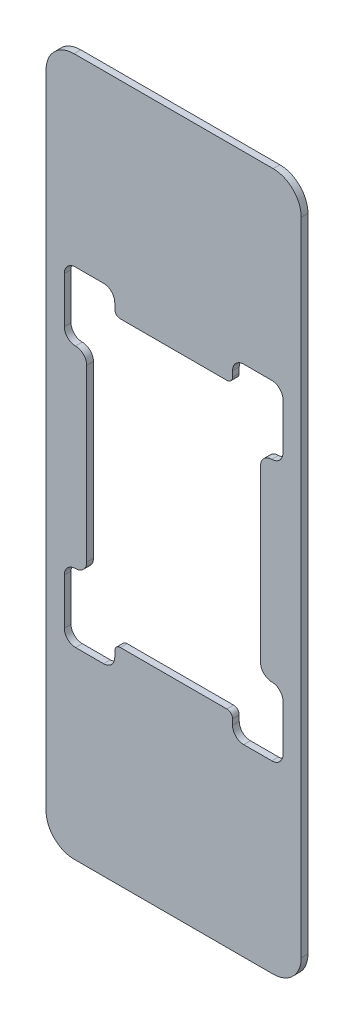
SolidWorks part; units mm, degrees
ref_plane "Front Plane" through (0, 0, 0) normal (0, 0, 1) x (1, 0, 0)
ref_plane "Top Plane" through (0, 0, 0) normal (0, 1, 0) x (1, 0, 0)
ref_plane "Right Plane" through (0, 0, 0) normal (1, 0, 0) x (0, 0, -1)
sketch "Sketch1" plane through (0, 0, 0) normal (0, 0, 1) x (1, 0, 0)
  line L1 (0, 0) -> (45.5, 0)
  line L2 (0, 0) -> (0, 124.4)
  line L3 (0, 124.4) -> (45.5, 124.4)
  line L4 (45.5, 0) -> (45.5, 124.4)
  dimension "D1" = 45.5
  dimension "D2" = 124.4
extrude "Boss-Extrude1" add sketch "Sketch1" along normal blind 1.2
sketch "Sketch2" plane through (0, 0, 1.2) normal (0, 0, 1) x (1, 0, 0)
  line L0 (22.75, 124.4) -> (22.75, 0) construction
  line L1 (45.5, 124.4) -> (0, 124.4) construction
  line L2 (0, 0) -> (45.5, 0) construction
  line L3 (0, 62.2) -> (45.5, 62.2) construction
  line L4 (0, 124.4) -> (0, 0) construction
  line L5 (45.5, 0) -> (45.5, 124.4) construction
  line L6 (42.25, 91.575) -> (33.25, 91.575)
  line L7 (7.25, 87.575) -> (38.25, 87.575)
  line L8 (7.25, 87.575) -> (7.25, 36.825)
  line L9 (7.25, 36.825) -> (38.25, 36.825)
  line L10 (38.25, 87.575) -> (38.25, 36.825)
  line L11 (7.25, 87.575) -> (38.25, 36.825) construction
  line L12 (7.25, 36.825) -> (38.25, 87.575) construction
  line L13 (3.25, 91.575) -> (12.25, 91.575)
  line L14 (3.25, 91.575) -> (3.25, 79.3895)
  line L15 (3.25, 79.3895) -> (12.25, 79.3895)
  line L16 (12.25, 91.575) -> (12.25, 79.3895)
  line L17 (42.25, 91.575) -> (42.25, 79.3895)
  line L18 (42.25, 79.3895) -> (33.25, 79.3895)
  line L19 (33.25, 91.575) -> (33.25, 79.3895)
  line L20 (33.25, 32.825) -> (33.25, 45.0105)
  line L21 (42.25, 45.0105) -> (33.25, 45.0105)
  line L22 (42.25, 32.825) -> (42.25, 45.0105)
  line L23 (42.25, 32.825) -> (33.25, 32.825)
  line L24 (3.25, 32.825) -> (12.25, 32.825)
  line L25 (3.25, 32.825) -> (3.25, 45.0105)
  line L26 (3.25, 45.0105) -> (12.25, 45.0105)
  line L27 (12.25, 32.825) -> (12.25, 45.0105)
  point P12 (22.75, 62.2)
  point P21 (0, 0)
  point P22 (19.272, 72.7135)
  dimension "D1" = 31
  dimension "D2" = 50.75
  dimension "D3" = 4
  dimension "D4" = 4
  dimension "D5" = 5
extrude "Cut-Extrude1" cut sketch "Sketch2" against normal blind 1.6 contours L16 L13 L14 L15 L8 L7 | L16 L7 L8 L15 | L27 L9 L20 L21 L10 L18 L19 L7 L16 L15 L8 L26 | L7 L19 L18 L10 | L6 L19 L7 L10 L18 L17 | L23 L22 L21 L10 L9 L20 | L10 L21 L20 L9 | L24 L27 L9 L8 L26 L25 | L9 L27 L26 L8 region at (38.9408, 86.673, 1.2) region at (22.75, 62.2, 1.2) region at (35.75, 83.4823, 1.2) region at (9.75, 83.4823, 1.2) region at (6.5592, 86.673, 1.2) region at (38.9408, 37.727, 1.2) region at (35.75, 40.9177, 1.2) region at (9.75, 40.9177, 1.2) region at (6.5592, 37.727, 1.2)
fillet "Fillet1" radius 2 16 edges at (3.25, 79.3895, 0.6) (12.25, 91.575, 0.6) (33.25, 91.575, 0.6) (42.25, 91.575, 0.6) (42.25, 79.3895, 0.6) (38.25, 79.3895, 0.6) (38.25, 45.0105, 0.6) (42.25, 45.0105, 0.6) (42.25, 32.825, 0.6) (33.25, 32.825, 0.6) (12.25, 32.825, 0.6) (3.25, 32.825, 0.6) (3.25, 45.0105, 0.6) (7.25, 45.0105, 0.6) (7.25, 79.3895, 0.6) (3.25, 91.575, 0.6)
fillet "Fillet2" radius 1 4 edges at (33.25, 36.825, 0.6) (12.25, 36.825, 0.6) (12.25, 87.575, 0.6) (33.25, 87.575, 0.6)
fillet "Fillet3" radius 5 4 edges at (0, 0, 0.6) (45.5, 0, 0.6) (45.5, 124.4, 0.6) (0, 124.4, 0.6)
